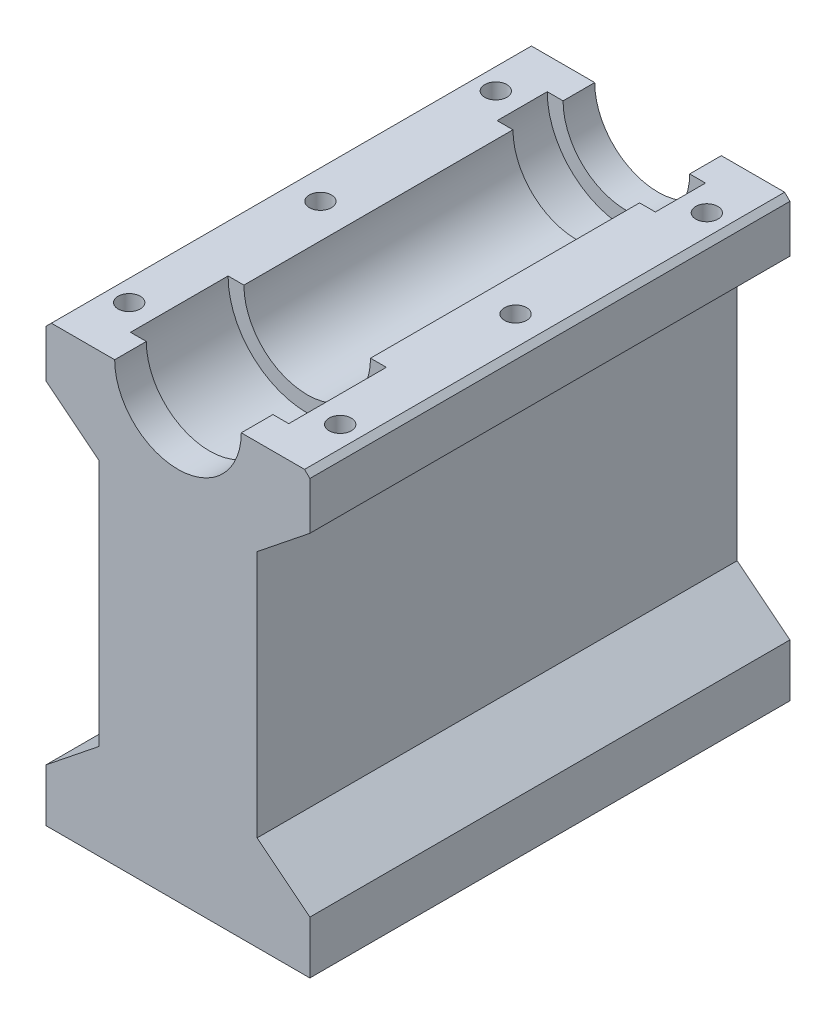
SolidWorks part; units mm, degrees
material "2024-T361"
ref_plane "Front Plane" through (0, 0, 0) normal (0, 0, 1) x (1, 0, 0)
ref_plane "Top Plane" through (0, 0, 0) normal (0, 1, 0) x (1, 0, 0)
ref_plane "Right Plane" through (0, 0, 0) normal (1, 0, 0) x (0, 0, -1)
sketch "Sketch1" plane through (0, 0, 0) normal (0, 0, 1) x (1, 0, 0)
  line L0 (12, 0) -> (25, 0)
  line L1 (25, 0) -> (25, -10)
  line L2 (25, -83) -> (-25, -83)
  line L3 (-25, -83) -> (-25, -73)
  line L4 (-25, 0) -> (-12, 0)
  line L5 (25, -10) -> (15, -18)
  line L6 (15, -18) -> (15, -65)
  line L7 (15, -65) -> (25, -73)
  line L8 (-25, -10) -> (-15, -18)
  line L9 (-15, -18) -> (-15, -65)
  line L10 (-15, -65) -> (-25, -73)
  line L13 (25, -73) -> (25, -83)
  line L14 (-25, -10) -> (-25, 0)
  arc A0 (-12, 0) -> (12, 0) centre (0, 0) ccw
  point P10 (0, -12)
  dimension "D1" = 8
  dimension "D3" = 50
  dimension "D4" = 12
  dimension "D2" = 10
  dimension "D5" = 83
  dimension "D6" = 8
  dimension "D7" = 10
  dimension "D8" = 30
extrude "Boss-Extrude1" add sketch "Sketch1" against normal blind 91
ref_axis "Ось1" through (0, 0, -91) along (0, 0, 1)
sketch "Sketch8" plane through (0, 0, 0) normal (0, 1, 0) x (1, 0, 0)
  line L1 (12, 91) -> (12, 0) construction
  line L2 (12, 85) -> (15, 85)
  line L3 (12, 85) -> (12, 75.5)
  line L4 (12, 75.5) -> (15, 75.5)
  line L5 (15, 85) -> (15, 75.5)
  line L7 (12, 91) -> (12, 0) construction
  line L8 (12, 24.5) -> (15, 24.5)
  line L9 (12, 24.5) -> (12, 6)
  line L10 (12, 6) -> (15, 6)
  line L11 (15, 24.5) -> (15, 6)
  line L12 (25, 0) -> (12, 0) construction
  dimension "D1" = 6
  dimension "D2" = 9.5
  dimension "D3" = 15
  dimension "D4" = 51
  dimension "D5" = 18.5
revolve "Cut-Revolve2" cut sketch "Sketch8" angle 360 about axis through (0, 0, -91) along (0, 0, 1)
hole_wizard "Отверстие обработанное метчиком M5x0.81" positions "Sketch5" profile "Sketch6" tap size "M5x0.8" standard "Ansi Metric" end condition up to next
sketch "Sketch5" plane through (0, 0, 0) normal (0, 1, 0) x (1, 0, 0)
  line L0 (-15, 80.25) -> (-25, 80.25) construction
  line L4 (15, 80.25) -> (25, 80.25) construction
  line L8 (-12, 45.5) -> (-25, 45.5) construction
  line L15 (12, 45.5) -> (25, 45.5) construction
  line L18 (-25, 91) -> (-25, 0) construction
  line L19 (25, 91) -> (25, 0) construction
  line L21 (15, 85) -> (15, 75.5) construction
  line L22 (-15, 75.5) -> (-15, 85) construction
  line L27 (15, 10.75) -> (25, 10.75) construction
  line L29 (-15, 10.75) -> (-25, 10.75) construction
  line L33 (15, 24.5) -> (15, 6) construction
  line L34 (-12, 75.5) -> (-12, 24.5) construction
  line L35 (12, 75.5) -> (12, 24.5) construction
  point P0 (-20, 10.75)
  point P3 (20, 10.75)
  point P25 (-20, 80.25)
  point P27 (20, 80.25)
  point P46 (-18.5, 45.5)
  point P48 (18.5, 45.5)
cosmetic thread "Hole Thread1" parameters "D2"=5
cosmetic thread "Hole Thread2" parameters "D2"=5
cosmetic thread "Hole Thread3" parameters "D2"=5
cosmetic thread "Hole Thread4" parameters "D2"=5
cosmetic thread "Hole Thread5" parameters "D2"=5
cosmetic thread "Hole Thread6" parameters "D2"=5
sketch "Sketch6" plane through (-20, 0, -10.75) normal (1, 0, 0) x (0, 0, 1)
  line L0 (0, 0) -> (0, 14)
  line L1 (0, 14) -> (2.1, 14)
  line L2 (2.1, 14) -> (2.1, 0)
  line L5 (2.1, 0) -> (0, 0)
  line L11 (0, -6.35) -> (0, 107.95) construction
  dimension "Диаметр проходного сверла" = 4.2
  dimension "Глубина проходного сверла" = 14
ref_axis "Axis1" through (0, 0, -91) along (0, 0, 1)
sketch "Sketch9" plane through (0, -83, 0) normal (0, -1, 0) x (1, 0, 0)
  line L0 (0, -45.5) -> (0, -91) construction
  line L1 (-25, -91) -> (25, -91) construction
  line L2 (-25, -45.5) -> (25, -45.5) construction
  line L3 (-25, -91) -> (-25, 0) construction
  line L4 (25, -91) -> (25, 0) construction
  line L5 (0, 0) -> (0, -45.5) construction
  line L6 (-10, -20.275) -> (-10, -25.225) construction
  line L7 (-10, -25.225) -> (10, -25.225)
  line L8 (10, -20.275) -> (10, -25.225) construction
  line L9 (-10, -20.275) -> (10, -20.275)
  line L10 (-10, -65.775) -> (-10, -70.725) construction
  line L11 (-10, -25.225) -> (10, -20.275) construction
  line L12 (-10, -20.275) -> (10, -25.225) construction
  line L13 (-10, -65.775) -> (10, -65.775)
  line L14 (10, -65.775) -> (10, -70.725) construction
  line L15 (-10, -70.725) -> (10, -70.725)
  line L17 (-10, -65.775) -> (10, -70.725) construction
  line L18 (-10, -70.725) -> (10, -65.775) construction
  arc A0 (10, -65.775) -> (10, -70.725) centre (10, -68.25) cw
  arc A1 (-10, -65.775) -> (-10, -70.725) centre (-10, -68.25) ccw
  arc A2 (10, -20.275) -> (10, -25.225) centre (10, -22.75) cw
  arc A3 (-10, -20.275) -> (-10, -25.225) centre (-10, -22.75) ccw
  point P0 (0, -68.25)
  point P13 (0, -22.75)
  point P14 (0, -22.75)
  point P20 (0, -68.25)
extrude "Boss-Extrude2" add sketch "Sketch9" along normal blind 7
chamfer "Chamfer1" distance 0.5 angle 45 8 edges at (0, -90, -70.725) (-12.475, -90, -68.25) (0, -90, -65.775) (12.475, -90, -68.25) (0, -90, -25.225) (-12.475, -90, -22.75) (0, -90, -20.275) (12.475, -90, -22.75)
sketch "Sketch10" plane through (0, -83, 0) normal (0, -1, 0) x (1, 0, 0)
  line L0 (0, 0) -> (0, -20.5) construction
  line L1 (0, -61.5) -> (0, -91) construction
  line L2 (-25, -91) -> (25, -91) construction
  point P4 (0, -20.5)
  point P5 (0, -41)
  point P8 (0, -76.25)
  point P9 (0, -61.5)
  point P11 (0, -10.25)
chamfer "Фаска1" distance 1 angle 45 2 edges at (-25, 0, -45.5) (25, 0, -45.5)
sketch "Эскиз2" plane through (0, -83, 0) normal (0, -1, 0) x (1, 0, 0)
  line L0 (0, 0) -> (0, -20.275) construction
  line L3 (-10, -70.725) -> (10, -70.725) construction
  line L4 (10, -20.275) -> (-10, -20.275) construction
  line L5 (0, -20.275) -> (0, -70.725) construction
  line L6 (0, -70.725) -> (0, -91) construction
  line L7 (-25, -91) -> (25, -91) construction
  point P6 (0, -45.5)
  point P7 (0, -70.725)
  point P8 (0, -20.275)
  point P11 (0, -80.8625)
  point P15 (0, -10.1375)
hole_wizard "Отверстие обработанное метчиком M5x0.82" positions "Эскиз4" profile "Эскиз5" tap size "M5x0.8" standard "Ansi Metric"
sketch "Эскиз4" plane through (0, -83, 0) normal (0, -1, 0) x (-1, 0, 0)
  point P0 (0, 45.5)
  point P3 (0, 10.1375)
  point P6 (0, 80.8625)
sketch "Эскиз5" plane through (0, -83, -45.5) normal (1, 0, 0) x (0, 0, -1)
  line L0 (0, 0) -> (0, 18.6618)
  line L1 (0, 18.6618) -> (2.1, 17.4)
  line L2 (2.1, 17.4) -> (2.1, 0)
  line L5 (2.1, 0) -> (0, 0)
  line L10 (0, 18.6618) -> (-2.1, 17.4) construction
  line L11 (0, -6.35) -> (0, 107.95) construction
  dimension "Диаметр сверла" = 4.2
  dimension "Глубина сверла" = 17.4
  dimension "Угол заточки сверла" = 118
cosmetic thread "Отверстие резьбы1" parameters "D1"=15, "D2"=5
cosmetic thread "Отверстие резьбы2" parameters "D1"=15, "D2"=5
cosmetic thread "Отверстие резьбы3" parameters "D1"=15, "D2"=5
